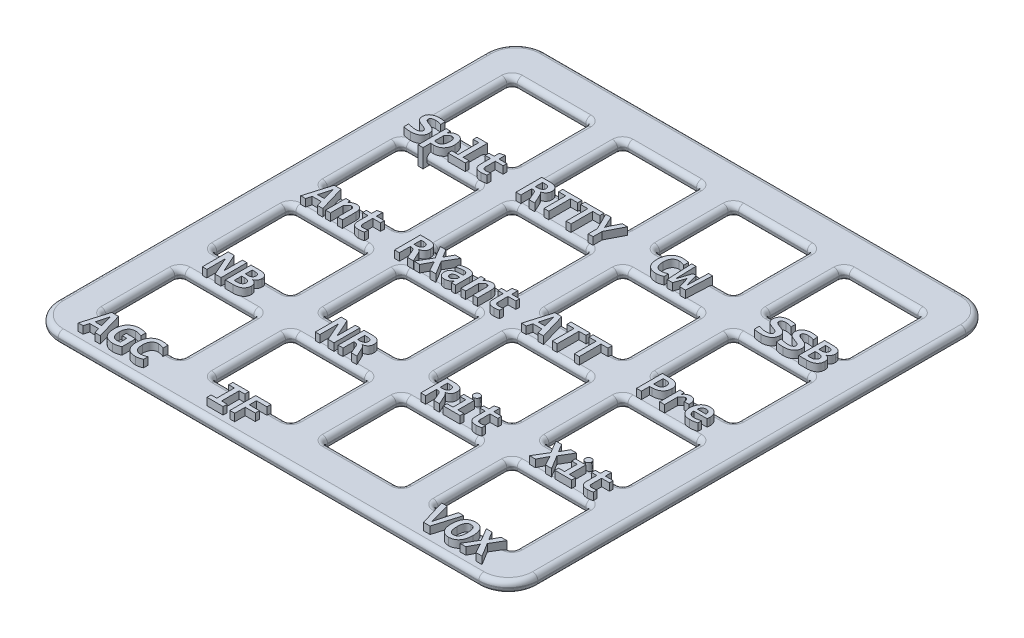
SolidWorks part; units mm, degrees
ref_plane "Front" through (0, 0, 0) normal (0, 0, 1) x (1, 0, 0)
ref_plane "Top" through (0, 0, 0) normal (0, 1, 0) x (1, 0, 0)
ref_plane "Right" through (0, 0, 0) normal (1, 0, 0) x (0, 0, -1)
sketch "Sketch1" plane through (0, 0, 0) normal (0, 1, 0) x (1, 0, 0)
  line L1 (-14.8807, -14.5355) -> (42.1193, -14.5355)
  line L2 (-18.8807, -18.5355) -> (-18.8807, -76.5355)
  line L3 (-14.8807, -80.5355) -> (42.1193, -80.5355)
  line L4 (46.1193, -18.5355) -> (46.1193, -76.5355)
  arc A0 (-14.8807, -14.5355) -> (-18.8807, -18.5355) centre (-14.8807, -18.5355) ccw
  arc A1 (46.1193, -18.5355) -> (42.1193, -14.5355) centre (42.1193, -18.5355) ccw
  arc A2 (42.1193, -80.5355) -> (46.1193, -76.5355) centre (42.1193, -76.5355) ccw
  arc A3 (-18.8807, -76.5355) -> (-14.8807, -80.5355) centre (-14.8807, -76.5355) ccw
  dimension "D1" = 65
  dimension "D2" = 66
extrude "main" add sketch "Sketch1" along normal blind 1.5
sketch "Sketch2" plane through (0, 1.5, 0) normal (0, 1, 0) x (1, 0, 0)
  line L0 (42.1193, -14.5355) -> (-14.8807, -14.5355) construction
  line L1 (-14.2307, -19.6855) -> (-3.5307, -19.6855)
  line L2 (-14.2307, -19.6855) -> (-14.2307, -30.3855)
  line L3 (-14.2307, -30.3855) -> (-3.5307, -30.3855)
  line L4 (-3.5307, -19.6855) -> (-3.5307, -30.3855)
  line L5 (-18.8807, -18.5355) -> (-18.8807, -76.5355) construction
  point P4 (-8.8807, -19.6855)
  dimension "D1" = 5.15
  dimension "D2" = 4.65
  dimension "D3" = 10.7
  dimension "D4" = 10.7
extrude "button hole 1" cut sketch "Sketch2" against normal through all
fillet "button fillet" radius 0.7 12 edges at (-8.8807, 0, 30.3855) (-8.8807, 1.5, 30.3855) (-8.8807, 0, 19.6855) (-8.8807, 1.5, 19.6855) (-3.5307, 0.75, 30.3855) (-3.5307, 0, 25.0355) (-3.5307, 0.75, 19.6855) (-3.5307, 1.5, 25.0355) (-14.2307, 0.75, 19.6855) (-14.2307, 0, 25.0355) (-14.2307, 0.75, 30.3855) (-14.2307, 1.5, 25.0355)
pattern_linear "buttons by 16" count 4 spacing 15 along (1, 0, 0) count 4 spacing 15 along (0, 0, 1) of "button fillet", "button hole 1"
fillet "outer edge fillet" radius 0.7 16 edges at (13.6193, 1.5, 14.5355) (13.6193, 0, 14.5355) (46.1193, 1.5, 47.5355) (46.1193, 0, 47.5355) (13.6193, 1.5, 80.5355) (13.6193, 0, 80.5355) (-18.8807, 1.5, 47.5355) (-18.8807, 0, 47.5355) (44.9477, 1.5, 15.7071) (44.9477, 1.5, 79.364) (-17.7092, 1.5, 79.364) (-17.7092, 1.5, 15.7071) (44.9477, 0, 15.7071) (44.9477, 0, 79.364) (-17.7092, 0, 79.364) (-17.7092, 0, 15.7071)
sketch "Lettering" plane through (0, 0, 0) normal (0, 1, 0) x (1, 0, 0)
  line L0 (45.4193, -49.1355) -> (-18.1807, -49.1355) construction
  line L1 (45.4783, -79.1355) -> (-16.5217, -79.1355) construction
  line L2 (45.4193, -76.5355) -> (45.4193, -18.5355) construction
  line L3 (-18.1807, -18.5355) -> (-18.1807, -76.5355) construction
  line L4 (16.4693, -48.9855) -> (25.7693, -48.9855) construction
  line L5 (45.4193, -64.1355) -> (-18.1807, -64.1355) construction
  line L6 (45.4193, -76.5355) -> (45.4193, -18.5355) construction
  line L7 (-18.1807, -18.5355) -> (-18.1807, -76.5355) construction
  line L8 (45.4193, -34.1355) -> (-18.1807, -34.1355) construction
  line L11 (-14.8807, -80.5355) -> (42.1193, -80.5355) construction
  text T0 "SSB" font "Consolas" height 3.5
  text T1 "CW" font "Consolas" height 3.5
  text T2 "RTTY" font "Consolas" height 3.5
  text T3 "Splt" font "Consolas" height 3.5
  text T4 "Xit" font "Consolas" height 3.5
  text T5 "Rit" font "Consolas" height 3.5
  text T6 "NB" font "Consolas" height 3.5
  text T7 "NR" font "Consolas" height 3.5
  text T8 "VOX" font "Consolas" height 3.5
  text T9 "RXant" font "Consolas" height 3.5
  text T10 "Pre" font "Consolas" height 3.5
  text T11 "AGC" font "Consolas" height 3.5
  text T12 "ATT" font "Consolas" height 3.5
  text T13 "IF\r\n" font "Consolas" height 3.5
  text T14 "Ant" font "Consolas" height 3.5
  dimension "D1" = 46.4
  dimension "D2" = 16.4
  dimension "D3" = 1.4
  dimension "D4" = 31.4
extrude "lettering boss" add sketch "Lettering" along normal blind 2.5
